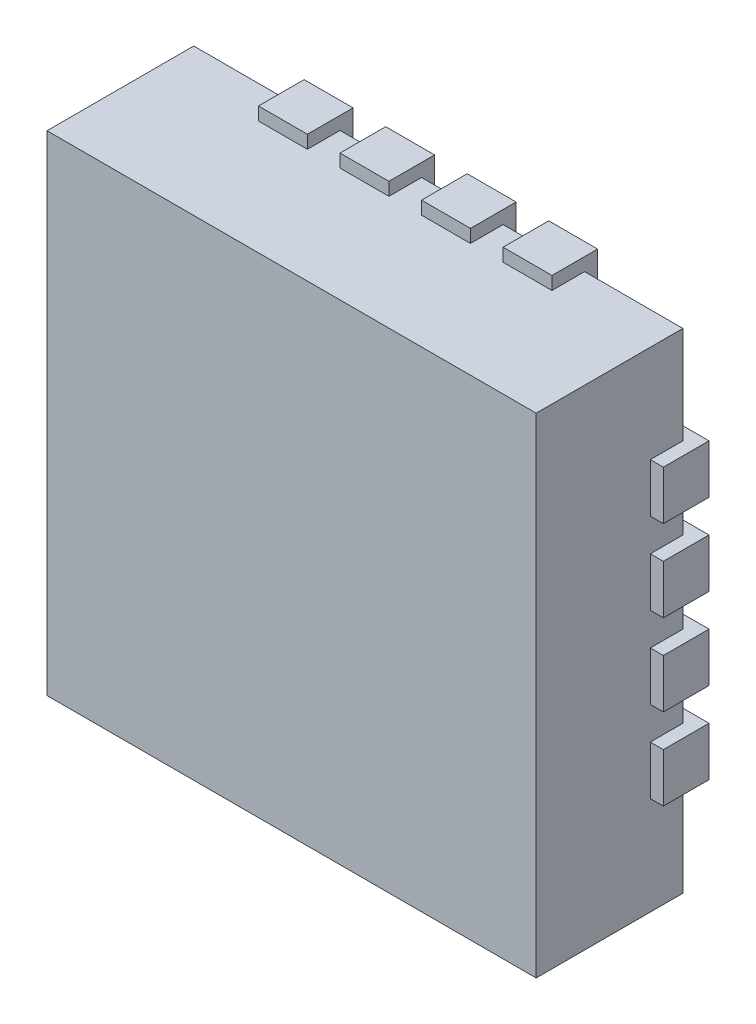
SolidWorks part; units mm, degrees
ref_plane "Front Plane" through (0, 0, 0) normal (0, 0, 1) x (1, 0, 0)
ref_plane "Top Plane" through (0, 0, 0) normal (0, 1, 0) x (1, 0, 0)
ref_plane "Right Plane" through (0, 0, 0) normal (1, 0, 0) x (0, 0, -1)
sketch "Sketch1" plane through (0, 0, 0) normal (0, 0, 1) x (1, 0, 0)
  line L1 (0, 0) -> (3, 0)
  line L2 (0, 0) -> (0, 3)
  line L3 (0, 3) -> (3, 3)
  line L4 (3, 0) -> (3, 3)
  dimension "D1" = 3
  dimension "D2" = 3
extrude "Boss-Extrude1" add sketch "Sketch1" along normal blind 0.9
sketch "Sketch2" plane through (0, 0, 0) normal (0, 0, -1) x (-1, 0, 0)
  line L0 (-1.5, 3) -> (-1.5, 0) construction
  line L1 (-3, 3) -> (0, 3) construction
  line L2 (0, 0) -> (-3, 0) construction
  line L3 (-1.247, 3.08) -> (-1.247, 2.7) construction
  line L4 (-3, 0) -> (-3, 3) construction
  line L5 (-3, 1.5) -> (0, 1.5) construction
  line L6 (0, 3) -> (0, 0) construction
  line L7 (-1.397, 3.08) -> (-1.097, 3.08)
  line L8 (-1.397, 3.08) -> (-1.397, 2.85)
  line L9 (-0.897, 3.08) -> (-0.597, 3.08)
  line L10 (-1.097, 3.08) -> (-1.097, 2.85)
  line L11 (-0.897, 3.08) -> (-0.897, 2.85)
  line L12 (-0.597, 3.08) -> (-0.597, 2.85)
  line L13 (-0.747, 3.08) -> (-0.747, 2.7) construction
  line L14 (-1.397, 3.08) -> (-1.097, 3.08)
  line L15 (-1.397, 3.08) -> (-1.397, 2.85)
  line L16 (-1.097, 3.08) -> (-1.097, 2.85)
  line L17 (-1.247, 3.08) -> (-1.247, 2.7) construction
  line L18 (-1.897, 3.08) -> (-1.597, 3.08)
  line L19 (-1.897, 3.08) -> (-1.897, 2.85)
  line L20 (-1.597, 3.08) -> (-1.597, 2.85)
  line L21 (-1.747, 3.08) -> (-1.747, 2.7) construction
  line L22 (-1.897, 3.08) -> (-1.597, 3.08)
  line L23 (-1.897, 3.08) -> (-1.897, 2.85)
  line L24 (-1.597, 3.08) -> (-1.597, 2.85)
  line L25 (-1.747, 3.08) -> (-1.747, 2.7) construction
  line L26 (-2.397, 3.08) -> (-2.097, 3.08)
  line L27 (-2.397, 3.08) -> (-2.397, 2.85)
  line L28 (-2.097, 3.08) -> (-2.097, 2.85)
  line L29 (-2.247, 3.08) -> (-2.247, 2.7) construction
  arc A0 (-1.397, 2.85) -> (-1.097, 2.85) centre (-1.247, 2.85) ccw
  arc A1 (-0.897, 2.85) -> (-0.597, 2.85) centre (-0.747, 2.85) ccw
  arc A2 (-1.397, 2.85) -> (-1.097, 2.85) centre (-1.247, 2.85) ccw
  arc A3 (-1.897, 2.85) -> (-1.597, 2.85) centre (-1.747, 2.85) ccw
  arc A4 (-1.897, 2.85) -> (-1.597, 2.85) centre (-1.747, 2.85) ccw
  arc A5 (-2.397, 2.85) -> (-2.097, 2.85) centre (-2.247, 2.85) ccw
  dimension "D4" = 0.15
  dimension "D1" = 0.08
  dimension "D2" = 0.253
  dimension "D3" = 0.3
  dimension "D5" = 0.15
  dimension "D6" = 2
  dimension "D7" = 3
extrude "Boss-Extrude2" add sketch "Sketch2" along normal blind 0.08 separate body contours L10 A0 L8 L7 | L11 A1 L12 L9 | L20 A3 L19 L18 | L28 A5 L27 L26
sketch "Sketch3" plane through (0, 0, 0) normal (0, 0, 1) x (1, 0, 0)
  line L0 (3, 3) -> (0, 3) construction
  line L1 (0.597, 3.08) -> (0.897, 3.08)
  line L2 (0.597, 3.08) -> (0.597, 3)
  line L3 (0.597, 3) -> (0.897, 3)
  line L4 (0.897, 3.08) -> (0.897, 3)
  line L5 (0.897, 3.08) -> (0.897, 2.85) construction
  line L6 (1.397, 3.08) -> (1.397, 2.85) construction
  line L7 (1.097, 3.08) -> (1.397, 3.08)
  line L8 (1.097, 3.08) -> (1.097, 3)
  line L9 (1.097, 3) -> (1.397, 3)
  line L10 (1.397, 3.08) -> (1.397, 3)
  line L11 (1.897, 3.08) -> (1.897, 2.85) construction
  line L12 (1.597, 3.08) -> (1.897, 3.08)
  line L13 (1.597, 3.08) -> (1.597, 3)
  line L14 (1.597, 3) -> (1.897, 3)
  line L15 (1.897, 3.08) -> (1.897, 3)
  line L16 (2.397, 3.08) -> (2.397, 2.85) construction
  line L17 (2.097, 3.08) -> (2.397, 3.08)
  line L18 (2.097, 3.08) -> (2.097, 3)
  line L19 (2.097, 3) -> (2.397, 3)
  line L20 (2.397, 3.08) -> (2.397, 3)
extrude "Boss-Extrude3" add sketch "Sketch3" along normal blind 0.2
ref_plane "Plane1" through (0, 0, 0) normal (-0.7071, 0.7071, 0) x (0, 0, 1)
ref_plane "Plane2" through (1.5, 1.5, 0) normal (-0.7071, -0.7071, 0) x (-0.7071, 0.7071, 0)
ref_axis "Axis1" through (1.5, 1.5, -0.045) along (0, 0, 1)
pattern_circular "CirPattern1" count 4 over 360 about axis through (1.5, 1.5, -0.045) along (0, 0, 1) of "Boss-Extrude2", "Boss-Extrude3"
